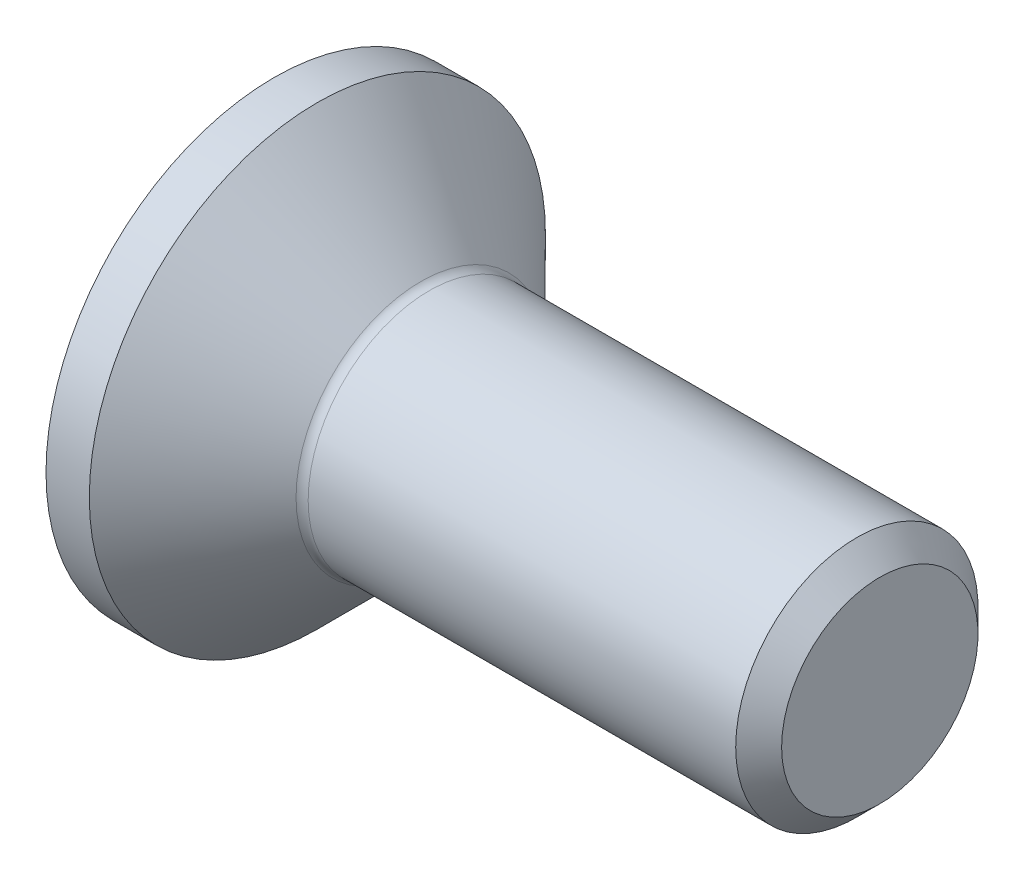
SolidWorks part; units mm, degrees
ref_plane "Front" through (0, 0, 0) normal (0, 0, 1) x (1, 0, 0)
ref_plane "Top" through (0, 0, 0) normal (0, 1, 0) x (1, 0, 0)
ref_plane "Right" through (0, 0, 0) normal (1, 0, 0) x (0, 0, -1)
sketch "Sketch1" plane through (0, 0, 0) normal (0, 0, 1) x (1, 0, 0)
  line L0 (0, 0) -> (0, 4.48)
  line L1 (0, 4.48) -> (2.48, 2)
  line L2 (2.48, 2) -> (10, 2)
  line L3 (10, 2) -> (10, 0)
  line L4 (10, 0) -> (0, 0)
  line L5 (-0.5871, 0) -> (5.4927, 0) construction
  dimension "D1" = 45
  dimension "l" = 10
  dimension "k" = 2.48
  dimension "d" = 4
revolve "Base" add sketch "Sketch1" angle 360 about L5
cosmetic thread "ThreadCosmetic1" [suppressed] parameters "b"=7.5, "D2"=3.242
sketch "Sketch2" plane through (0, 0, 0) normal (1, 0, 0) x (0, 0, -1)
  line L1 (1.4434, 0) -> (0.7217, 1.25)
  line L2 (0.7217, 1.25) -> (-0.7217, 1.25)
  line L3 (-0.7217, 1.25) -> (-1.4434, 0)
  line L4 (-1.4434, 0) -> (-0.7217, -1.25)
  line L5 (-0.7217, -1.25) -> (0.7217, -1.25)
  line L6 (0.7217, -1.25) -> (1.4434, 0)
  circle A0 centre (0, 0) radius 1.25 construction
  dimension "s" = 2.5
extrude "HexagonSocket" cut sketch "Sketch2" along normal blind 1.5
sketch "Sketch3" plane through (0, 0, 0) normal (0, 0, 1) x (1, 0, 0)
  line L0 (-0.4391, 0) -> (4.425, 0) construction
  line L1 (1.5, 0) -> (1.5, -1.25) construction
  line L2 (1.5, 1.25) -> (2.2217, 0)
  line L3 (2.2217, 0) -> (1.5, -1.25) construction
  line L4 (1.5, 1.25) -> (1.5, 0)
  line L5 (1.5, 0) -> (2.2217, 0)
  line L7 (1.5, 1.25) -> (1.5, 0) construction
  dimension "D1" = 120
revolve "Cut-Revolve1" cut sketch "Sketch3" angle 360 about L0
fillet "HeadFillet" radius 0.2 1 edges at (2.48, 0, 2)
chamfer "Chamfer" distance 0.379 angle 45 1 edges at (10, 0, 2)
sketch "Sketch4" plane through (0, 0, 0) normal (0, 1, 0) x (1, 0, 0)
  line L0 (11.8531, 0) -> (-2.694, 0) construction
  line L1 (-2, 8.765) -> (3, 8.765)
  line L2 (-2, 8.765) -> (-2, 3.765)
  line L3 (-2, 3.765) -> (3, 3.765)
  line L4 (3, 8.765) -> (3, 3.765)
  line L5 (0, 4.48) -> (0, -4.48) construction
  dimension "dk" = 7.53
  dimension "D2" = 2
  dimension "D3" = 5
  dimension "D4" = 5
revolve "Cut-Revolve2" cut sketch "Sketch4" angle 360 about L0
sketch "Sketch5" plane through (0, 0, 0) normal (0, 0, 1) x (1, 0, 0)
  line L0 (9.621, 1.6718) -> (9.8105, 2)
  line L1 (9.8105, 2) -> (9.8105, 2.379)
  line L2 (9.8105, 2.379) -> (9.4315, 2.379)
  line L3 (9.4315, 2.379) -> (9.4315, 2)
  line L4 (9.4315, 2) -> (9.621, 1.6718)
  line L5 (0, 0) -> (10.6885, 0) construction
  line L6 (9.621, 2) -> (9.621, -2) construction
  dimension "D1" = 4
  dimension "D2" = 0.379
revolve "Cut-Revolve10" [suppressed] cut sketch "Sketch5" angle 360 about L5
pattern_linear "LPattern10" [suppressed] count 16 spacing 0.4548 along (-1, 0, 0) of bodies 105
equation "\"D1@Chamfer\" = (  \"d@Sketch1\" - \"D2@ThreadCosmetic1\" )  / 2"
equation "\"D1@Sketch5\" = \"d@Sketch1\""
equation "\"D2@Sketch5\" =  ( \"d@Sketch1\" - \"D2@ThreadCosmetic1\" )  / 2"
equation "\"D3@LPattern10\" = \"D2@Sketch5\" * 1.2"
equation "\"D1@LPattern10\" = \"b@ThreadCosmetic1\" / \"D3@LPattern10\""
